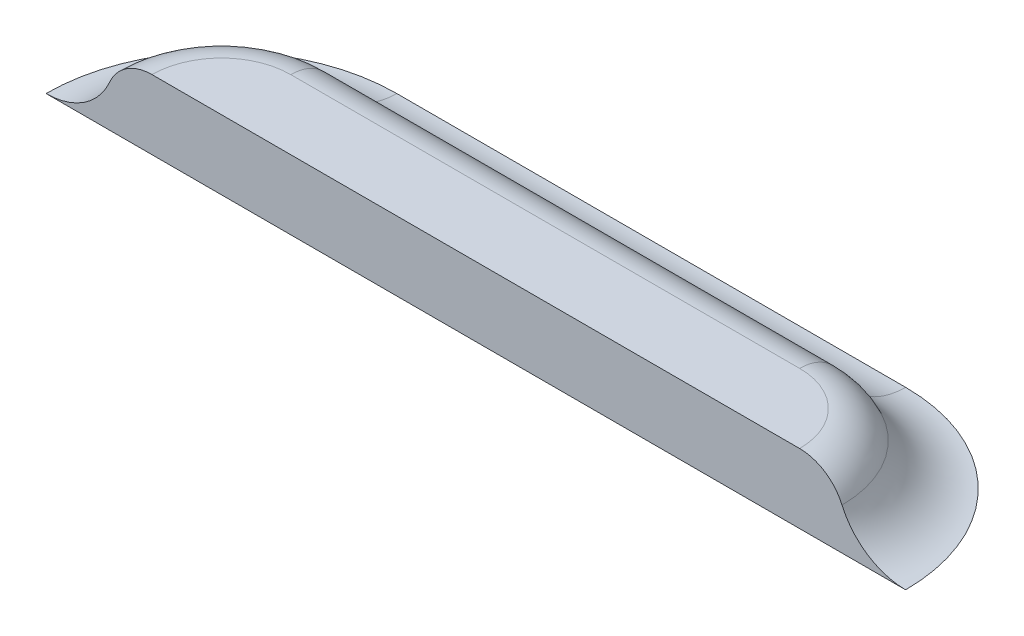
SolidWorks part; units mm, degrees
ref_plane "Front Plane" through (0, 0, 0) normal (0, 0, 1) x (1, 0, 0)
ref_plane "Top Plane" through (0, 0, 0) normal (0, 1, 0) x (1, 0, 0)
ref_plane "Right Plane" through (0, 0, 0) normal (1, 0, 0) x (0, 0, -1)
sketch "Sketch1" plane through (0, 0, 0) normal (0, 1, 0) x (1, 0, 0)
  line L1 (76.2, -25.4) -> (-76.2, -25.4)
  line L2 (76.2, -25.4) -> (76.2, 25.4)
  line L3 (76.2, 25.4) -> (-76.2, 25.4)
  line L4 (-76.2, -25.4) -> (-76.2, 25.4)
  line L5 (76.2, -25.4) -> (-76.2, 25.4) construction
  line L6 (76.2, 25.4) -> (-76.2, -25.4) construction
  point P0 (0, 0)
  dimension "D1" = 152.4
  dimension "D2" = 50.8
extrude "Boss-Extrude1" add sketch "Sketch1" along normal blind 9.525
sketch "Sketch2" plane through (0, 9.525, 0) normal (0, 1, 0) x (1, 0, 0)
  line L1 (50.8, -7.9375) -> (-50.8, -7.9375)
  line L2 (50.8, -7.9375) -> (50.8, 7.9375)
  line L3 (50.8, 7.9375) -> (-50.8, 7.9375)
  line L4 (-50.8, -7.9375) -> (-50.8, 7.9375)
  line L5 (50.8, -7.9375) -> (-50.8, 7.9375) construction
  line L6 (50.8, 7.9375) -> (-50.8, -7.9375) construction
  point P0 (0, 0)
  dimension "D1" = 101.6
  dimension "D2" = 15.875
extrude "Boss-Extrude2" add sketch "Sketch2" along normal blind 9.525
fillet "Fillet1" radius 15.875 2 edges at (-50.8, 14.2875, -7.9375) (50.8, 14.2875, -7.9375)
fillet "Fillet2" radius 6.35 3 edges at (46.1503, 19.05, -3.2878) (-46.1503, 19.05, -3.2878) (0, 19.05, -7.9375)
fillet "Fillet3" radius 9.525 3 edges at (-46.1503, 9.525, -3.2878) (46.1503, 9.525, -3.2878) (0, 9.525, -7.9375)
sketch "Sketch3" plane through (0, 9.525, 0) normal (0, 1, 0) x (1, 0, 0)
  line L4 (-76.2, 25.4) -> (-76.2, -25.4)
  line L5 (-76.2, -25.4) -> (76.2, -25.4)
  line L6 (76.2, -25.4) -> (76.2, 25.4)
  line L7 (76.2, 25.4) -> (-76.2, 25.4)
  line L8 (-76.2, 25.4) -> (-76.2, -25.4)
  line L9 (-76.2, -25.4) -> (76.2, -25.4)
  line L10 (76.2, -25.4) -> (76.2, 25.4)
  line L11 (76.2, 25.4) -> (-76.2, 25.4)
  dimension "D1" = 0
extrude "Cut-Extrude1" cut sketch "Sketch3" against normal through all
sketch "Orientation Sketch" plane through (0, 9.525, 0) normal (0, -1, 0) x (-1, 0, 0)
  line L0 (34.925, 16.1372) -> (-34.925, 16.1372) construction
  line L1 (58.9997, -7.9375) -> (-58.9997, -7.9375) construction
  line L2 (34.925, 16.1372) -> (-34.925, 16.1372)
  line L3 (58.9997, -7.9375) -> (-58.9997, -7.9375)
  arc A0 (58.9997, -7.9375) -> (34.925, 16.1372) centre (34.925, -7.9375) ccw construction
  arc A1 (-34.925, 16.1372) -> (-58.9997, -7.9375) centre (-34.925, -7.9375) ccw construction
  arc A2 (58.9997, -7.9375) -> (34.925, 16.1372) centre (34.925, -7.9375) ccw
  arc A3 (-34.925, 16.1372) -> (-58.9997, -7.9375) centre (-34.925, -7.9375) ccw
  point P5 (0, 4.0998)
other "FormTool1"
